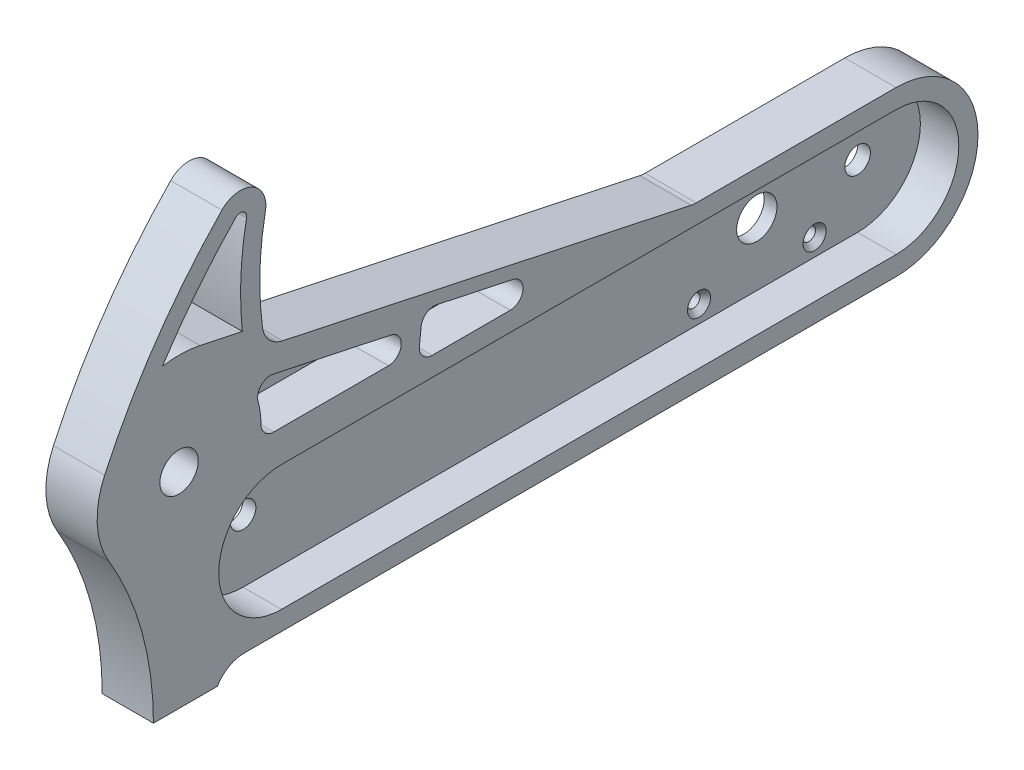
SolidWorks part; units mm, degrees
material "UHMW Polyethylene"
ref_plane "Front Plane" through (0, 0, 0) normal (0, 0, 1) x (1, 0, 0)
ref_plane "Top Plane" through (0, 0, 0) normal (0, 1, 0) x (1, 0, 0)
ref_plane "Right Plane" through (0, 0, 0) normal (1, 0, 0) x (0, 0, -1)
ref_plane "Plane1" through (44.45, 0, 0) normal (1, 0, 0) x (0, 0, -1)
sketch "Sketch1" plane through (44.45, 0, 0) normal (1, 0, 0) x (0, 0, -1)
  line L0 (0, 20.32) -> (-50.1918, 20.32)
  line L1 (-50.1918, 20.32) -> (-156.3872, 42.8925)
  line L2 (-184.15, -24.13) -> (-168.275, -24.13)
  line L3 (-177.8, -24.13) -> (-177.8, 26.67) construction
  line L4 (-161.6759, -20.32) -> (0, -20.32)
  line L5 (-210.1467, 95.3503) -> (7.8853, 24.145) construction
  line L6 (0, -25.4) -> (-249.5816, -25.4) construction
  arc A0 (-195.2627, 16.2798) -> (-196.2562, 35.1713) centre (-177.8, 26.67) cw
  arc A1 (-196.2562, 35.1713) -> (-167.1767, 77.5725) centre (-57.8348, -28.5883) cw
  arc A2 (-167.1767, 77.5725) -> (-156.3872, 71.9389) centre (-162.6208, 73.1492) cw
  arc A4 (-184.15, -24.13) -> (-195.2627, 16.2798) centre (-263.1786, -24.13) ccw
  arc A6 (-168.275, -24.13) -> (-161.6759, -20.32) centre (-161.6759, -27.94) cw
  arc A7 (0, -20.32) -> (0, 20.32) centre (0, 0) ccw
  circle A8 centre (0, 0) radius 25.4 construction
  circle A9 centre (-177.8, 26.67) radius 52.07 construction
  circle A10 centre (-161.6351, 76.1673) radius 3.175 construction
  arc A11 (-156.3872, 71.9389) -> (-156.3872, 42.8925) centre (-81.584, 57.4157) ccw
  circle A12 centre (-177.8, 26.67) radius 4.7625
  circle A13 centre (-152.4, 0) radius 3.175
  circle A14 centre (0, 0) radius 3.175
  circle A15 centre (-25.0031, 0) radius 5
  dimension "D1" = 6.35
  dimension "D2" = 152.4
  dimension "D6" = 7.62
  dimension "D3" = 76.2
  dimension "D12" = 9.525
  dimension "D13" = 6.35
  dimension "D8" = 10
  dimension "D4" = 15.875
  dimension "D5" = 6.35
  dimension "D9" = 5.08
  dimension "D10" = 31.75
  dimension "D11" = 1.27
  dimension "D7" = 12
extrude "Boss-Extrude1" add sketch "Sketch1" along normal blind 12.7
sketch "Sketch6" plane through (57.15, 0, 0) normal (1, 0, 0) x (0, 0, -1)
  line L0 (-35.4758, -20.32) -> (-14.5304, -20.32)
  line L1 (-35.4758, 20.32) -> (-14.5304, 20.32)
  line L2 (0, 20.32) -> (-50.1918, 20.32) construction
  line L3 (-161.6759, -20.32) -> (0, -20.32) construction
  arc A0 (-35.4758, -20.32) -> (-14.5304, -20.32) centre (-25.0031, 0) ccw
  circle A1 centre (-25.0031, 0) radius 5 construction
  arc A2 (-14.5304, 20.32) -> (-35.4758, 20.32) centre (-25.0031, 0) ccw
  dimension "D1" = 22.86
extrude "28mm motor support" [suppressed] add sketch "Sketch6" against normal up to surface (12.7 mm away) up to face at (44.45, 18.3967, 128.7869)
sketch "Sketch4" plane through (57.15, 0, 0) normal (1, 0, 0) x (0, 0, -1)
  line L0 (-157.7296, 23.495) -> (-95.6708, 23.495)
  line L1 (-95.6708, 23.495) -> (-160.4619, 37.2668)
  line L3 (-50.1918, 20.32) -> (-156.3872, 42.8925) construction
  line L4 (0, 20.32) -> (-50.1918, 20.32) construction
  arc A0 (-160.4619, 37.2668) -> (-157.7296, 23.495) centre (-177.8, 26.67) cw
  arc A2 (-196.2562, 35.1713) -> (-195.2627, 16.2798) centre (-177.8, 26.67) ccw construction
  dimension "D1" = 3.175
  dimension "D2" = 6.35
extrude "Cut-Extrude3" cut sketch "Sketch4" against normal offset from surface (10.16 mm away) 2.54 up to face at (44.45, 18.3967, 128.7869)
fillet "Fillet2" radius 3.175 3 edges at (52.07, 23.495, 95.6708) (52.07, 23.495, 157.7296) (52.07, 37.2668, 160.4619)
sketch "Sketch5" plane through (57.15, 0, 0) normal (1, 0, 0) x (0, 0, -1)
  line L0 (-113.9556, 30.6275) -> (-95.0107, 26.6006)
  line L1 (-95.6708, 20.32) -> (-115.0389, 20.32)
  line L2 (0, 20.32) -> (-50.1918, 20.32) construction
  line L3 (-50.1918, 20.32) -> (-156.3872, 42.8925) construction
  line L4 (-117.7733, 27.8537) -> (-118.1965, 23.8269)
  line L5 (-95.6708, 23.495) -> (-125.8789, 26.67) construction
  arc A0 (-113.9556, 30.6275) -> (-117.7733, 27.8537) centre (-114.6157, 27.5219) ccw
  arc A1 (-118.1965, 23.8269) -> (-115.0389, 20.32) centre (-115.0389, 23.495) ccw
  arc A2 (-95.6708, 20.32) -> (-95.0107, 26.6006) centre (-95.6708, 23.495) ccw
  arc A4 (-125.8789, 23.495) -> (-125.2188, 29.7756) centre (-125.8789, 26.67) ccw construction
  point P20 (-122.7213, 26.3381)
  dimension "D2" = 3.175
  dimension "D1" = 3.175
  dimension "D3" = 4.7625
extrude "Cut-Extrude4" cut sketch "Sketch5" against normal up to surface (10.16 mm away) up to face at (46.99, 28.5995, 145.7216)
sketch "Sketch2" plane through (57.15, 0, 0) normal (1, 0, 0) x (0, 0, -1)
  line L0 (-173.5752, 46.546) -> (-156.3872, 42.8925)
  line L1 (-172.5851, 51.2044) -> (-162.1055, 48.9769)
  arc A0 (-196.2562, 35.1713) -> (-173.5752, 46.546) centre (-177.8, 26.67) cw
  arc A1 (-196.2562, 35.1713) -> (-195.2627, 16.2798) centre (-177.8, 26.67) ccw construction
  arc A2 (-167.1767, 77.5725) -> (-196.2562, 35.1713) centre (-57.8348, -28.5883) ccw construction
  arc A3 (-156.3872, 71.9389) -> (-156.3872, 42.8925) centre (-81.584, 57.4157) ccw construction
  arc A4 (-156.3872, 71.9389) -> (-167.1767, 77.5725) centre (-162.6208, 73.1492) ccw construction
  arc A5 (-156.3872, 71.9389) -> (-156.3872, 42.8925) centre (-81.584, 57.4157) ccw
  arc A6 (-156.3872, 71.9389) -> (-167.1767, 77.5725) centre (-162.6208, 73.1492) ccw
  arc A7 (-167.1767, 77.5725) -> (-196.2562, 35.1713) centre (-57.8348, -28.5883) ccw
  arc A8 (-161.0624, 72.8466) -> (-162.1055, 48.9769) centre (-81.584, 57.4157) ccw
  arc A9 (-161.0624, 72.8466) -> (-163.7597, 74.255) centre (-162.6208, 73.1492) ccw
  arc A10 (-163.7597, 74.255) -> (-181.9186, 51.4121) centre (-57.8348, -28.5883) ccw
  arc A11 (-181.9186, 51.4121) -> (-172.5851, 51.2044) centre (-177.8, 26.67) cw
  dimension "D1" = 4.7625
extrude "Cut-Extrude1" cut sketch "Sketch2" against normal up to surface (12.7 mm away) contours A10 A11 L1 A8 A9 region at (57.15, 59.6657, 168.7495) up to face at (44.45, 18.3967, 128.7869)
sketch "Sketch3" plane through (57.15, 0, 0) normal (1, 0, 0) x (0, 0, -1)
  line L0 (-152.4, 15.5575) -> (0, 15.5575)
  line L1 (0, -15.5575) -> (-152.4, -15.5575)
  line L2 (0, 20.32) -> (-50.1918, 20.32) construction
  arc A0 (0, 15.5575) -> (0, -15.5575) centre (0, 0) cw
  arc A1 (-152.4, -15.5575) -> (-152.4, 15.5575) centre (-152.4, 0) cw
  arc A3 (0, -20.32) -> (0, 20.32) centre (0, 0) ccw construction
  circle A4 centre (-152.4, 0) radius 25.4 construction
  dimension "D1" = 4.7625
extrude "Cut-Extrude2" cut sketch "Sketch3" against normal offset from surface (9.525 mm away) 3.175 up to face at (44.45, 18.3967, 128.7869)
fillet "Fillet1" radius 6.35 2 edges at (50.8, 42.8925, 156.3872) (50.8, 20.32, 50.1918)
hole_wizard "CSK for #4 Flat Head Machine Screw1" positions "Sketch7" profile "Sketch8" countersink size "#4" standard "ANSI Inch" end condition up to next
sketch "Sketch7" plane through (47.625, 0, 0) normal (1, 0, 0) x (0, 0, -1)
  point P0 (-39.326, 11.2776)
  point P3 (-10.6802, 11.2776)
  point P6 (-10.6802, -11.2776)
  point P9 (-39.326, -11.2776)
sketch "Sketch8" plane through (47.625, 11.2776, 39.326) normal (0, 1, 0) x (0, 0, -1)
  line L0 (0, 0) -> (0, 3.175)
  line L1 (0, 3.175) -> (1.6319, 3.175)
  line L2 (1.6319, 3.175) -> (1.6319, 1.4098)
  line L3 (1.6319, 1.4098) -> (2.8575, 0)
  line L5 (2.8575, 0) -> (0, 0)
  line L6 (-1.6319, 1.4098) -> (-2.8575, 0) construction
  line L11 (0, -6.35) -> (0, 107.95) construction
  dimension "Thru Hole Dia." = 3.2639
  dimension "Thru Hole Depth" = 3.175
  dimension "Near C'Sink Dia." = 5.715
  dimension "Near C'Sink Angle" = 82
equation "\"D8@Sketch1\"=10mm"
